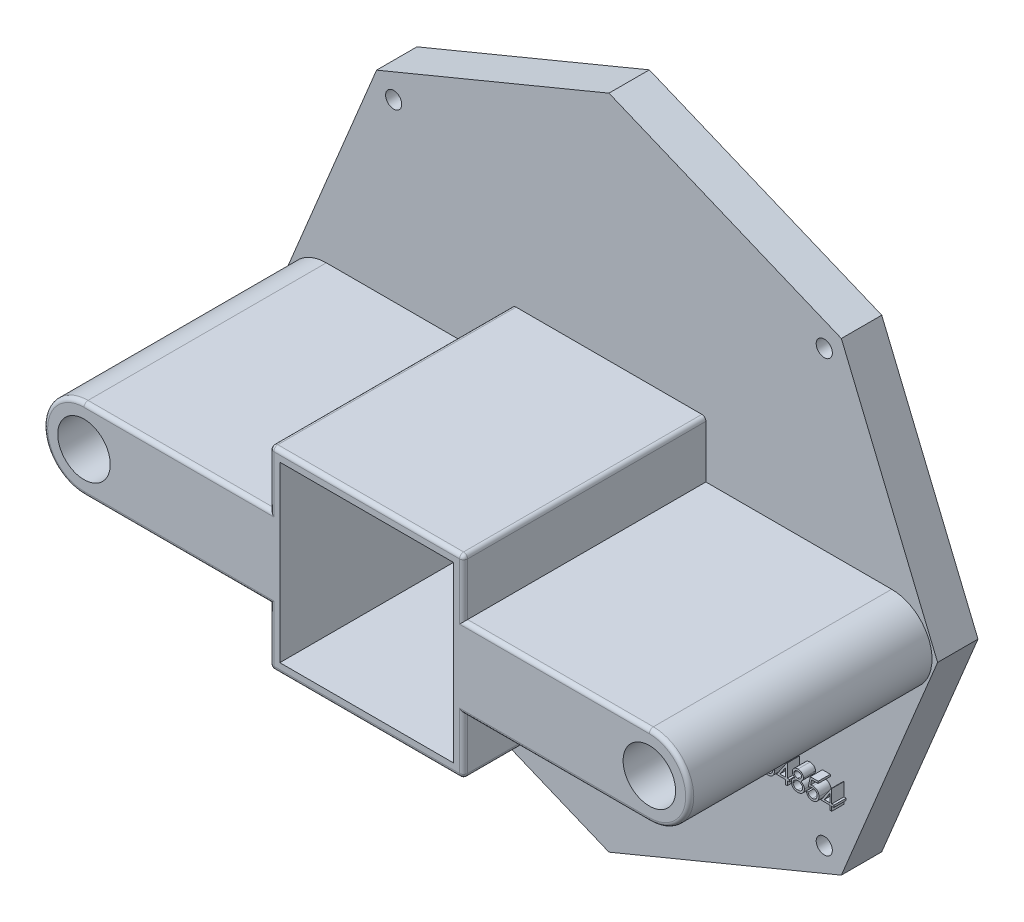
SolidWorks part; units mm, degrees
ref_plane "Front Plane" through (0, 0, 0) normal (0, 0, 1) x (1, 0, 0)
ref_plane "Top Plane" through (0, 0, 0) normal (0, 1, 0) x (1, 0, 0)
ref_plane "Right Plane" through (0, 0, 0) normal (1, 0, 0) x (0, 0, -1)
sketch "Sketch1" plane through (0, 0, 0) normal (0, 0, 1) x (1, 0, 0)
  line L0 (-70, 0) -> (70, 0)
  line L1 (0, 0) -> (0, 15.4939)
  line L2 (-81.3906, 0) -> (-57.5518, -57.5518)
  line L3 (-57.5518, -57.5518) -> (0, -81.3906)
  line L4 (0, -81.3906) -> (57.5518, -57.5518)
  line L5 (57.5518, -57.5518) -> (81.3906, 0)
  line L6 (81.3906, 0) -> (57.5518, 57.5518)
  line L7 (57.5518, 57.5518) -> (0, 81.3906)
  line L8 (0, 81.3906) -> (-57.5518, 57.5518)
  line L9 (-57.5518, 57.5518) -> (-81.3906, 0)
  line L10 (-57.5518, 57.5518) -> (0, 0) construction
  line L11 (57.5518, 57.5518) -> (0, 0) construction
  line L12 (57.5518, -57.5518) -> (0, 0) construction
  line L13 (-57.5518, -57.5518) -> (0, 0) construction
  line L15 (-21.5, -21.5) -> (21.5, -21.5)
  line L16 (-21.5, -21.5) -> (-21.5, 21.5)
  line L17 (-21.5, 21.5) -> (21.5, 21.5)
  line L18 (21.5, -21.5) -> (21.5, 21.5)
  line L19 (-21.5, -21.5) -> (21.5, 21.5) construction
  line L20 (-21.5, 21.5) -> (21.5, -21.5) construction
  line L21 (-24, -24) -> (24, -24)
  line L22 (-24, -24) -> (-24, 24)
  line L23 (-24, 24) -> (24, 24)
  line L24 (24, -24) -> (24, 24)
  line L25 (-24, -24) -> (24, 24) construction
  line L26 (-24, 24) -> (24, -24) construction
  circle A0 centre (-70, 0) radius 6.5
  circle A1 centre (70, 0) radius 6.5
  circle A2 centre (0, 0) radius 75.1951 construction
  circle A3 centre (-70, 0) radius 10
  circle A4 centre (70, 0) radius 10
  circle A5 centre (-53.3199, 53.3199) radius 2
  circle A6 centre (53.3199, 53.3199) radius 2
  circle A7 centre (53.3199, -53.3199) radius 2
  circle A8 centre (-53.3199, -53.3199) radius 2
  point P4 (0, 0)
  dimension "D1" = 13
  dimension "D2" = 13
  dimension "D5" = 20
  dimension "D6" = 4
  dimension "D3" = 140
  dimension "D4" = 162.7811
  dimension "D7" = 43
  dimension "D8" = 43
  dimension "D9" = 48
extrude "Boss-Extrude1" add sketch "Sketch1" along normal blind 10 contours L8 L9 L2 L3 L4 L5 L6 L7 A6 A5 A4 L24 L21 L22 A3 L23 A7 A8 region at (-67.3444, 27.8949, 0)
sketch "Sketch2" plane through (0, 0, 0) normal (0, 0, 1) x (1, 0, 0)
  line L1 (-21.5, -21.5) -> (21.5, -21.5)
  line L2 (-21.5, -21.5) -> (-21.5, 21.5)
  line L3 (-21.5, 21.5) -> (21.5, 21.5)
  line L4 (21.5, -21.5) -> (21.5, 21.5)
  line L5 (-21.5, -21.5) -> (21.5, 21.5) construction
  line L6 (-21.5, 21.5) -> (21.5, -21.5) construction
  line L7 (-24, -24) -> (24, -24)
  line L8 (-24, -24) -> (-24, 24)
  line L9 (-24, 24) -> (24, 24)
  line L10 (24, -24) -> (24, 24)
  line L11 (-24, -24) -> (24, 24) construction
  line L12 (-24, 24) -> (24, -24) construction
  point P0 (0, 0)
  point P6 (0, 0)
  dimension "D1" = 43
  dimension "D2" = 43
  dimension "D3" = 48
extrude "Boss-Extrude2" add sketch "Sketch2" along normal blind 70
sketch "Sketch3" plane through (0, 0, 10) normal (0, 0, 1) x (1, 0, 0)
  line L0 (70, 0) -> (-70, 0)
  circle A0 centre (70, 0) radius 10
  circle A1 centre (-70, 0) radius 10
  circle A2 centre (70, 0) radius 6.5
  circle A3 centre (-70, 0) radius 6.5
  point P4 (0, 0)
  circle M1 centre (70, 0) radius 10
  circle M12 centre (-70, 0) radius 10
  dimension "D2" = 13
  dimension "D3" = 13
  dimension "D1" = 140
extrude "Boss-Extrude3" add sketch "Sketch3" along normal blind 60 and the other way blind 10 contours A2 M1 | A3 M12 region at (70, 9.7172, 10) region at (-79.7172, 0, 10)
sketch "Sketch4" plane through (0, 0, 10) normal (0, 0, 1) x (1, 0, 0)
  line L0 (70, -10) -> (22, -10)
  line L1 (70, 10) -> (22, 10)
  line L2 (22, 10) -> (22, -10)
  line L3 (-70, -10) -> (-22, -10)
  line L4 (-70, 10) -> (-22, 10)
  line L5 (-22, -10) -> (-22, 10)
  circle A0 centre (70, 0) radius 10
  circle A1 centre (-70, 0) radius 10
  circle M2 centre (70, 0) radius 10
  line M5 (-24, -24) -> (-24, 24)
  line M9 (24, 24) -> (24, -24)
  circle M13 centre (-70, 0) radius 10
  dimension "D1" = 48
  dimension "D3" = 48
extrude "Boss-Extrude4" add sketch "Sketch4" along normal blind 60 contours L1 L0 M2 M9 | L4 L3 M13 M5 region at (43.1383, 0, 10) region at (-43.1383, 0, 10)
fillet "Fillet4" radius 1 10 edges at (-24, -24, 40) (24, -24, 40) (24, -17, 70) (0, -24, 70) (-24, -17, 70) (-24, 17, 70) (-24, 24, 40) (24, 24, 40) (0, 24, 70) (24, 17, 70)
fillet "Fillet5" radius 1 6 edges at (80, 0, 70) (-80, 0, 70) (-46.5, 10, 70) (46.5, 10, 70) (46.5, -10, 70) (-46.5, -10, 70)
sketch "Sketch5" plane through (0, 0, 10) normal (0, 0, 1) x (1, 0, 0)
  text T0 "       BENJAMIN GREEN  10479271\r\nVASILEIOS CHATZIMARKOS 10454854" font "Century Gothic" height in points 18
extrude "Boss-Extrude5" add sketch "Sketch5" against normal blind 3 and the other way blind 3
